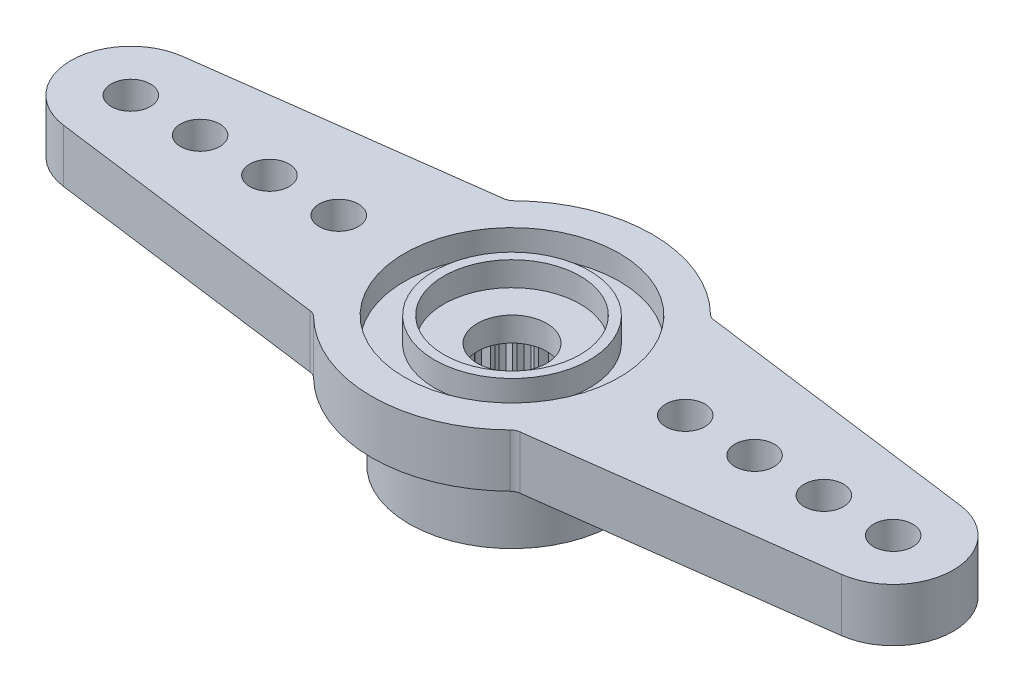
SolidWorks part; units mm, degrees
material "PA Type 6"
ref_plane "Plan de face" through (0, 0, 0) normal (0, 0, 1) x (1, 0, 0)
ref_plane "Plan de dessus" through (0, 0, 0) normal (0, 1, 0) x (1, 0, 0)
ref_plane "Plan de droite" through (0, 0, 0) normal (1, 0, 0) x (0, 0, -1)
ref_axis "Axe1" through (0, 0, 0) along (0, 1, 0)
sketch "Esquisse1" plane through (0, 0, 0) normal (0, 1, 0) x (1, 0, 0)
  line L0 (-19.1, 0) -> (19.1, 0) construction
  line L1 (0, 0) -> (0, -8.9896) construction
  line L2 (-16.8394, 2.5778) -> (-4.3707, 4.2193)
  line L3 (-16.8394, -2.5778) -> (-4.3707, -4.2193)
  line L4 (16.8394, -2.5778) -> (4.3707, -4.2193)
  line L5 (16.8394, 2.5778) -> (4.3707, 4.2193)
  circle A0 centre (0, 0) radius 19.1 construction
  circle A1 centre (0, 0) radius 6.075
  arc A2 (-16.8394, 2.5778) -> (-16.8394, -2.5778) centre (-16.5, 0) ccw
  circle A3 centre (-16.5, 0) radius 0.85
  circle A4 centre (-13.5, 0) radius 0.85
  circle A5 centre (-10.5, 0) radius 0.85
  circle A6 centre (-7.5, 0) radius 0.85
  circle A7 centre (7.5, 0) radius 0.85
  circle A8 centre (10.5, 0) radius 0.85
  circle A9 centre (13.5, 0) radius 0.85
  circle A10 centre (16.5, 0) radius 0.85
  arc A11 (16.8394, 2.5778) -> (16.8394, -2.5778) centre (16.5, 0) cw
  circle A12 centre (0, 0) radius 4.65
  circle A13 centre (0, 0) radius 1.5
  circle A14 centre (0, 0) radius 3.35
  circle A15 centre (0, 0) radius 2.95
  dimension "D1" = 38.2
  dimension "D2" = 12.15
  dimension "D3" = 1.7
  dimension "D9" = 9.3
  dimension "D10" = 6.7
  dimension "D11" = 0.4
  dimension "D12" = 3
  dimension "D4" = 3
  dimension "D5" = 3
  dimension "D6" = 3
  dimension "D7" = 33
  dimension "D8" = 15
sketch "Esquisse2" plane through (0, 0, 0) normal (0, 0, 1) x (1, 0, 0)
  line L0 (0, 3.9296) -> (0, -5.2174) construction
  line L1 (21.01, 0) -> (-21.01, 0) construction
  line L2 (0, -3.5) -> (-4.45, -3.5)
  line L3 (0, -3.5) -> (0, 2.1)
  line L4 (0, 2.1) -> (-4.45, 2.1)
  line L5 (-4.45, -3.5) -> (-4.45, 2.1)
  point P9 (-4.45, -0.2)
  dimension "D1" = 8.9
  dimension "D2" = 3.5
  dimension "D3" = 3.3
  dimension "D4" = 2.3
revolve "Révolution1" add sketch "Esquisse2" angle 360 about L0
sketch "Esquisse3" plane through (0, 2.1, 0) normal (0, 1, 0) x (1, 0, 0)
  line L0 (-16.8394, 2.5778) -> (-4.3707, 4.2193) construction
  line L1 (-16.8394, -2.5778) -> (-4.3707, -4.2193) construction
  line L2 (-16.8394, 2.5778) -> (-4.3707, 4.2193)
  line L3 (-16.8394, -2.5778) -> (-4.3707, -4.2193)
  line L4 (0, 0) -> (0, -8.9896) construction
  line L5 (0, 0) -> (0, -8.9896) construction
  line L6 (16.8394, -2.5778) -> (4.3707, -4.2193)
  line L7 (16.8394, 2.5778) -> (4.3707, 4.2193)
  arc A0 (-16.8394, 2.5778) -> (-16.8394, -2.5778) centre (-16.5, 0) ccw construction
  circle A1 centre (-16.5, 0) radius 0.85 construction
  circle A2 centre (-13.5, 0) radius 0.85 construction
  circle A3 centre (-10.5, 0) radius 0.85 construction
  circle A4 centre (-7.5, 0) radius 0.85 construction
  circle A5 centre (0, 0) radius 6.075 construction
  arc A6 (-16.8394, 2.5778) -> (-16.8394, -2.5778) centre (-16.5, 0) ccw
  circle A7 centre (-16.5, 0) radius 0.85
  circle A8 centre (-13.5, 0) radius 0.85
  circle A9 centre (-10.5, 0) radius 0.85
  circle A10 centre (-7.5, 0) radius 0.85
  arc A11 (-4.3707, -4.2193) -> (4.3707, -4.2193) centre (0, 0) ccw
  circle A12 centre (7.5, 0) radius 0.85
  circle A13 centre (10.5, 0) radius 0.85
  circle A14 centre (13.5, 0) radius 0.85
  circle A15 centre (16.5, 0) radius 0.85
  arc A16 (16.8394, 2.5778) -> (16.8394, -2.5778) centre (16.5, 0) cw
  arc A17 (4.3707, 4.2193) -> (-4.3707, 4.2193) centre (0, 0) ccw
extrude "Boss.-Extru.1" add sketch "Esquisse3" against normal up to vertex (2.3 mm away) up to point (-4.45, -0.2, 0)
fillet "Congé1" radius 0.5 4 edges at (4.3707, 0.95, -4.2193) (4.3707, 0.95, 4.2193) (-4.3707, 0.95, 4.2193) (-4.3707, 0.95, -4.2193)
sketch "Esquisse4" plane through (0, 2.1, 0) normal (0, 1, 0) x (1, 0, 0)
  circle A0 centre (0, 0) radius 2.95 construction
  circle A1 centre (0, 0) radius 2.95
extrude "Enlèv. mat.-Extru.1" cut sketch "Esquisse4" against normal blind 1.05
sketch "Esquisse5" plane through (0, 2.1, 0) normal (0, 1, 0) x (1, 0, 0)
  circle A0 centre (0, 0) radius 3.35 construction
  circle A1 centre (0, 0) radius 4.65 construction
  circle A2 centre (0, 0) radius 3.35
  circle A3 centre (0, 0) radius 4.65
extrude "Enlèv. mat.-Extru.2" cut sketch "Esquisse5" against normal blind 1.05
sketch "Esquisse6" plane through (0, -3.5, 0) normal (0, -1, 0) x (1, 0, 0)
  circle A0 centre (0, 0) radius 1.5 construction
  circle A1 centre (0, 0) radius 1.5
extrude "Enlèv. mat.-Extru.3" cut sketch "Esquisse6" against normal through all
sketch "Esquisse7" plane through (0, 0, 0) normal (0, 1, 0) x (1, 0, 0)
  line L6 (0.1267, -2.9973) -> (0.2711, -2.6537)
  line L7 (0.3973, -2.6377) -> (0.6227, -2.9347)
  line L8 (0, 0) -> (0, -3.7146) construction
  line L9 (0, 0) -> (0.3388, -2.6821) construction
  arc A4 (0.1267, -2.9973) -> (0.6227, -2.9347) centre (0, 0) ccw
  arc A5 (0.3973, -2.6377) -> (0.2711, -2.6537) centre (0.3388, -2.6821) ccw
  point P1 (0, 0)
  dimension "D2" = 6
  dimension "D7" = 0.37
  dimension "D4" = 0.5
  dimension "D5" = 7.2
  dimension "D6" = 60
sketch "Esquisse8" plane through (0, 0, 0) normal (0, 1, 0) x (1, 0, 0)
  circle A0 centre (0, 0) radius 2.68
  arc A1 (0.3973, -2.6377) -> (0.2711, -2.6537) centre (0.3388, -2.6821) ccw construction
  dimension "D1" = 0.05
extrude "Enlèv. mat.-Extru.4" cut sketch "Esquisse8" against normal through all
sketch "Esquisse9" plane through (0, 0, 0) normal (0, 1, 0) x (1, 0, 0)
  line L0 (0.1267, -2.9973) -> (0.2711, -2.6537) construction
  line L2 (0.1053, -3.0482) -> (0.2656, -2.6668)
  line L3 (-0.2656, -2.6668) -> (-0.1053, -3.0482)
  line L4 (0, -2.4923) -> (0, -2.738) construction
  line L5 (0, 0) -> (0, -3.7146) construction
  arc A0 (-0.1053, -3.0482) -> (0.1053, -3.0482) centre (0, 0) ccw
  circle A1 centre (0, 0) radius 2.68
  arc A2 (-0.2656, -2.6668) -> (0.2656, -2.6668) centre (0, 0) ccw
  arc A3 (0.1267, -2.9973) -> (0.6227, -2.9347) centre (0, 0) ccw construction
  dimension "D2" = 0.05
  dimension "D1" = 0
extrude "Enlèv. mat.-Extru.5" cut sketch "Esquisse9" against normal through all
pattern_circular "Répétition circulaire1" count 25 over 360 about axis through (0, 0, 0) along (0, 1, 0) of "Enlèv. mat.-Extru.5"
